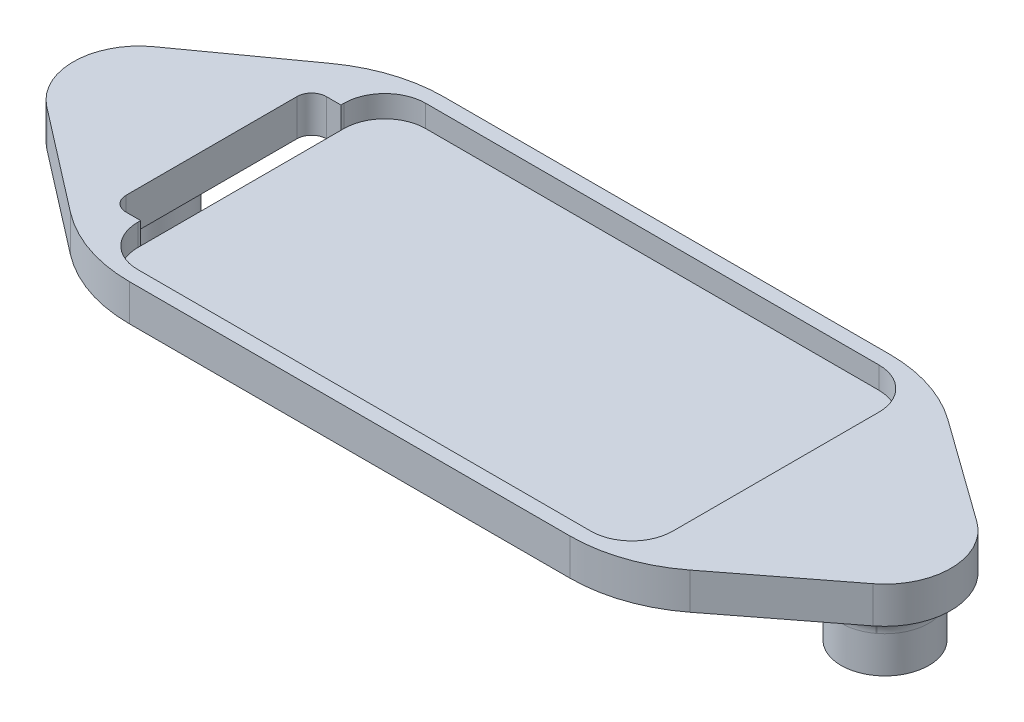
SolidWorks part; units mm, degrees
ref_plane "前视基准面" through (0, 0, 0) normal (0, 0, 1) x (1, 0, 0)
ref_plane "上视基准面" through (0, 0, 0) normal (0, 1, 0) x (1, 0, 0)
ref_plane "右视基准面" through (0, 0, 0) normal (1, 0, 0) x (0, 0, -1)
sketch "草图1" plane through (0, 0, 0) normal (0, 1, 0) x (1, 0, 0)
  line L0 (-19.79, 11.345) -> (-19.79, 6.845)
  line L1 (-15.49, 9.845) -> (15.49, 9.845)
  line L2 (-18.29, 7.045) -> (-18.29, -7.045)
  line L3 (-15.49, -9.845) -> (15.49, -9.845)
  line L4 (18.29, 7.045) -> (18.29, -7.045)
  line L5 (-18.29, 9.845) -> (18.29, -9.845) construction
  line L6 (-18.29, -9.845) -> (18.29, 9.845) construction
  line L10 (19.79, 11.345) -> (19.79, -11.345)
  line L11 (-19.79, 11.345) -> (19.79, -11.345) construction
  line L12 (-19.79, -11.345) -> (19.79, 11.345) construction
  line L13 (-19.79, -11.345) -> (-19.79, -6.845)
  line L15 (-18.29, 6.845) -> (-20.29, 6.845)
  line L16 (-20.29, 6.845) -> (-20.29, -6.845)
  line L17 (-20.29, -6.845) -> (-18.29, -6.845)
  line L18 (0, 11.345) -> (0, -11.345)
  line L19 (-19.79, 11.345) -> (19.79, 11.345)
  line L28 (-19.79, -11.345) -> (19.79, -11.345)
  line L29 (19.79, -11.345) -> (32.204, -0.5383)
  line L30 (19.79, 11.345) -> (32.204, 1.2471)
  line L31 (-19.79, 11.345) -> (-32.204, 1.2471)
  line L32 (-19.79, -11.345) -> (-32.204, -0.5383)
  line L33 (-19.79, 11.345) -> (-18.79, 11.345)
  line L34 (-18.79, 11.345) -> (-35.6127, -0.9376)
  line L35 (-18.79, -11.345) -> (-38.7537, 4.2776)
  line L36 (18.79, -11.345) -> (38.7537, 4.2776)
  line L37 (18.79, 11.345) -> (35.6127, -0.9376)
  line L38 (-4.4179, 9.845) -> (-4.4179, 10.845)
  line L39 (-4.4179, 10.845) -> (-19.79, 10.845)
  line L40 (-4.4179, 10.845) -> (19.79, 10.845)
  line L41 (-11.7494, -9.845) -> (-11.7494, -10.845)
  line L42 (-11.7494, -10.845) -> (-19.79, -10.845)
  line L43 (-11.7494, -10.845) -> (19.79, -10.845)
  line L44 (-19.4748, 10.845) -> (-18.4748, 10.845)
  line L45 (-18.4748, 10.845) -> (-31.2019, 1.698)
  line L46 (-18.4748, -10.845) -> (-31.2019, -1.0299)
  line L47 (18.4748, -10.845) -> (31.2019, -1.0299)
  line L48 (18.4748, 10.845) -> (31.2019, 1.698)
  arc A0 (-18.29, -7.045) -> (-15.49, -9.845) centre (-15.49, -7.045) ccw
  arc A1 (15.49, -9.845) -> (18.29, -7.045) centre (15.49, -7.045) ccw
  arc A2 (18.29, 7.045) -> (15.49, 9.845) centre (15.49, 7.045) ccw
  arc A3 (-15.49, 9.845) -> (-18.29, 7.045) centre (-15.49, 7.045) ccw
  circle A4 centre (-25.5001, 0.2549) radius 3
  circle A17 centre (-25.5001, 0.2549) radius 4.4994
  circle A18 centre (25.5001, 0.2549) radius 4.4994
  point P0 (0, 0)
  point P7 (0, 0)
  point P32 (0, 0)
  point P47 (29.15, -4)
  point P50 (29.15, 4)
  point P59 (-29.15, -4)
  point P62 (-29.15, 4)
  dimension "D1" = 2.8
extrude "凸台-拉伸1" add sketch "草图1" along normal blind 1 contours A4 | A17 A4 | A17 L46 L13 L17 L16 L15 L0 L45 | A0 L2 L17 L13 L46 L42 L41 L3 | L41 L43 L18 L3 | L1 A3 L2 A0 L3 L18 | A3 L1 L38 L39 L45 L0 L15 L2 | L40 L38 L1 L18 | A2 L4 A1 L3 L18 L43 L47 L10 L48 L40 L1 | L4 A2 L1 L18 L3 A1 | L47 A18 L48 L10 | A18 region at (-19.0397, 0, -10.2434) region at (-20.0047, 0, -8.3724) region at (9.2374, 0, -10.5514) region at (-2.2089, 0, -10.345) region at (-23.5051, 0, -4.1455) region at (-9.0646, 0, 0) region at (9.0646, 0, 0) region at (-5.8747, 0, 10.345) region at (23.8327, 0, -6.7299) region at (-16.9143, 0, 9.5334) region at (25.5001, 0, -0.2549) region at (-25.5001, 0, -0.2549)
extrude "凸台-拉伸2" add sketch "草图1<3>" along normal blind 1.5 from surface contours A4 | A17 A4 | A17 L46 L13 L17 L16 L15 L0 L45 | A3 L1 L38 L39 L45 L0 L15 L2 | L40 L38 L1 L18 | A0 L2 L17 L13 L46 L42 L41 L3 | L41 L43 L18 L3 | A2 L4 A1 L3 L18 L43 L47 L10 L48 L40 L1 | L47 A18 L48 L10 | A18 region at (-19.0397, 0, -10.2434) region at (-20.0047, 0, -8.3724) region at (9.2374, 0, -10.5514) region at (-2.2089, 0, -10.345) region at (-23.5051, 0, -4.1455) region at (-5.8747, 0, 10.345) region at (23.8327, 0, -6.7299) region at (-16.9143, 0, 9.5334) region at (25.5001, 0, -0.2549) region at (-25.5001, 0, -0.2549) starting at face at (0, 1, -0.1578)
sketch "草图1<3>" plane through (0, 0, 0) normal (0, 1, 0) x (1, 0, 0) same geometry as "草图1"
fillet "圆角1" radius 1 2 edges at (-20.29, 1.25, 6.845) (-20.29, 1.25, -6.845)
extrude "凸台-拉伸3" add sketch "草图1<4>" against normal blind 4 from surface contours A4 region at (-25.5001, 0, -0.2549) starting at face at (0, 0, -0.1578)
sketch "草图1<4>" plane through (0, 0, 0) normal (0, 1, 0) x (1, 0, 0) same geometry as "草图1"
sketch "草图4" plane through (0, -4, 0) normal (0, -1, 0) x (1, 0, 0)
  circle A0 centre (-25.5001, -0.2549) radius 1.65
  circle A1 centre (25.5, -0.255) radius 1.65
extrude "切除-拉伸1" cut sketch "草图4" against normal blind 2.5
fillet "圆角2" radius 1.5 1 edges at (-25.5001, 0, 2.7451)
fillet "圆角3" radius 10 4 edges at (-18.4748, 1.25, 10.845) (18.4748, 1.25, 10.845) (18.4748, 1.25, -10.845) (-18.4748, 1.25, -10.845)
sketch "草图9" plane through (0, 0, 0) normal (0, -1, 0) x (1, 0, 0)
  circle A2 centre (25.5001, -0.2549) radius 3
extrude "凸台-拉伸6" add sketch "草图9" along normal blind 4
sketch "草图10" plane through (0, -4, 0) normal (0, -1, 0) x (1, 0, 0)
  circle A0 centre (25.5001, -0.2549) radius 2
extrude "切除-拉伸3" cut sketch "草图10" against normal blind 2.5
fillet "圆角5" radius 1.5 1 edges at (25.5001, 0, 2.7451)
